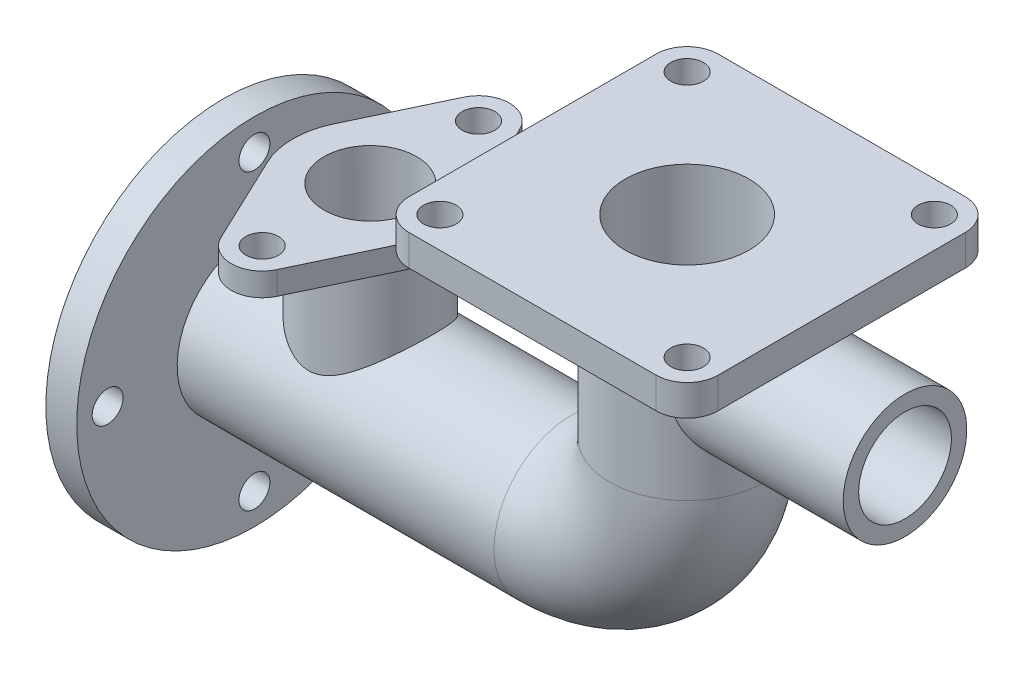
SolidWorks part; units mm, degrees
material "Titanium"
ref_plane "Front Plane" through (0, 0, 0) normal (0, 0, 1) x (1, 0, 0)
ref_plane "Top Plane" through (0, 0, 0) normal (0, 1, 0) x (1, 0, 0)
ref_plane "Right Plane" through (0, 0, 0) normal (1, 0, 0) x (0, 0, -1)
sketch "Sketch1" plane through (0, 0, 0) normal (0, 1, 0) x (1, 0, 0)
  circle A0 centre (0, 0) radius 10
  circle A1 centre (0, 0) radius 12.5
  dimension "D1" = 20
  dimension "D2" = 25
sketch "Sketch2" plane through (0, 0, 0) normal (0, 0, 1) x (1, 0, 0)
  line L0 (0, 0) -> (0, -31.25)
  line L1 (12.5, 0) -> (-12.5, 0) construction
  line L2 (-18.75, -50) -> (-75, -50)
  arc A0 (0, -31.25) -> (-18.75, -50) centre (-18.75, -31.25) cw
  dimension "D1" = 18.75
  dimension "D2" = 50
  dimension "D3" = 75
sweep "Sweep1" add profiles "Sketch1" path "Sketch2"
sketch "Sketch3" plane through (0, 0, 0) normal (0, 1, 0) x (1, 0, 0)
  line L1 (-20, 25) -> (20, 25)
  line L2 (-25, 20) -> (-25, -20)
  line L3 (-20, -25) -> (20, -25)
  line L4 (25, 20) -> (25, -20)
  line L5 (-25, 25) -> (25, -25) construction
  line L6 (-25, -25) -> (25, 25) construction
  arc A0 (20, -25) -> (25, -20) centre (20, -20) ccw
  arc A1 (20, 25) -> (25, 20) centre (20, 20) cw
  arc A2 (-25, -20) -> (-20, -25) centre (-20, -20) ccw
  arc A3 (-20, 25) -> (-25, 20) centre (-20, 20) ccw
  circle A4 centre (-20, 20) radius 2.64
  circle A5 centre (20, 20) radius 2.64
  circle A6 centre (-20, -20) radius 2.64
  circle A7 centre (20, -20) radius 2.64
  circle A8 centre (0, 0) radius 12.5 construction
  circle A9 centre (0, 0) radius 12.5
  point P0 (0, 0)
  dimension "D2" = 5
  dimension "D3" = 5.28
  dimension "D1" = 50
extrude "Boss-Extrude1" add sketch "Sketch3" against normal blind 5
sketch "Sketch4" plane through (0, 0, 0) normal (0, 0, 1) x (1, 0, 0)
  line L0 (0, -17.5) -> (35.25, -17.5) construction
  line L1 (0, -7.5) -> (35.25, -7.5)
  line L2 (0, -7.5) -> (0, -10)
  line L3 (0, -10) -> (35.25, -10)
  line L4 (35.25, -7.5) -> (35.25, -10)
  line L5 (25, 0) -> (20, 0) construction
  point P6 (0, -8.75)
  point P7 (0, 0)
  point P11 (0, 0)
  dimension "D1" = 15
  dimension "D2" = 20
  dimension "D3" = 17.5
  dimension "D4" = 35.25
revolve "Revolve1" add sketch "Sketch4" angle 360 about L0
sketch "Sketch5" plane through (0, 0, 0) normal (0, 0, 1) x (1, 0, 0)
  line L0 (0, -10) -> (35.25, -10) construction
  line L1 (0, -10) -> (35.25, -10)
  line L2 (0, -10) -> (0, -17.5)
  line L3 (0, -17.5) -> (35.25, -17.5)
  line L4 (35.25, -17.5) -> (35.25, -10)
revolve "Cut-Revolve1" cut sketch "Sketch5" angle 360 about L3
sketch "Sketch7" plane through (0, 0, 0) normal (0, 0, 1) x (1, 0, 0)
  line L0 (-75, -50) -> (-51.25, -50) construction
  line L1 (-61.25, -21.25) -> (-58.75, -21.25)
  line L2 (-61.25, -21.25) -> (-61.25, -50)
  line L3 (-61.25, -50) -> (-58.75, -50)
  line L4 (-58.75, -21.25) -> (-58.75, -50)
  line L5 (-75, -40) -> (-75, -60) construction
  line L6 (-18.75, -50) -> (-75, -50) construction
  line L7 (-51.25, -50) -> (-51.25, -21.25) construction
  point P10 (-53.1241, -21.25)
  point P12 (0, 0)
  point P13 (-51.25, -19.8357)
  dimension "D1" = 15
  dimension "D2" = 20
  dimension "D3" = 57.5
  dimension "D4" = 23.75
revolve "Revolve2" add sketch "Sketch7" angle 360 about L7
sketch "Sketch8" plane through (0, 0, 0) normal (0, 0, 1) x (1, 0, 0)
  line L0 (-58.75, -21.25) -> (-58.75, -50) construction
  line L1 (-58.75, -21.25) -> (-58.75, -50)
  line L2 (-58.75, -21.25) -> (-51.25, -21.25)
  line L3 (-51.25, -21.25) -> (-51.25, -50)
  line L4 (-51.25, -50) -> (-58.75, -50)
revolve "Cut-Revolve2" cut sketch "Sketch8" angle 360 about L3
sketch "Sketch9" plane through (0, -21.25, 0) normal (0, 1, 0) x (1, 0, 0)
  line L0 (-55.7675, 19.6429) -> (-62.5438, 5.3571)
  line L1 (-62.5438, -5.3571) -> (-55.7675, -19.6429)
  line L2 (-46.7325, -19.6429) -> (-39.9562, -5.3571)
  line L3 (-39.9562, 5.3571) -> (-46.7325, 19.6429)
  line L4 (-51.25, 17.5) -> (-51.25, -17.5) construction
  arc A0 (-62.5438, 5.3571) -> (-62.5438, -5.3571) centre (-51.25, 0) ccw
  arc A1 (-55.7675, -19.6429) -> (-46.7325, -19.6429) centre (-51.25, -17.5) ccw
  arc A2 (-39.9562, -5.3571) -> (-39.9562, 5.3571) centre (-51.25, 0) ccw
  arc A3 (-46.7325, 19.6429) -> (-55.7675, 19.6429) centre (-51.25, 17.5) ccw
  circle A4 centre (-51.25, 17.5) radius 2.64
  circle A5 centre (-51.25, -17.5) radius 2.64
  circle A6 centre (-51.25, 0) radius 10 construction
  circle A7 centre (-51.25, 0) radius 10
  point P2 (-51.25, 0)
  point P13 (-51.25, 0)
  dimension "D1" = 12.5
  dimension "D2" = 5
  dimension "D4" = 5.28
  dimension "D3" = 35
extrude "Boss-Extrude2" add sketch "Sketch9" against normal blind 3.75
sketch "Sketch10" plane through (-75, 0, 0) normal (-1, 0, 0) x (0, 0, 1)
  line L0 (-19.6429, -21.25) -> (-5.3571, -21.25) construction
  line L1 (-10, -50) -> (10, -50) construction
  circle A0 centre (0, -50) radius 28.75
  circle A1 centre (0, -50) radius 23.75 construction
  circle A2 centre (0, -26.25) radius 2.5
  circle A3 centre (23.75, -50) radius 2.5
  circle A4 centre (0, -73.75) radius 2.5
  circle A5 centre (-23.75, -50) radius 2.5
  circle A6 centre (0, -50) radius 10 construction
  circle A7 centre (0, -50) radius 12.5 construction
  circle A8 centre (0, -50) radius 12.5
  point P5 (0, -50)
  point P19 (0, -50)
  dimension "D1" = 47.5
  dimension "D2" = 5
  dimension "D3" = 4
extrude "Boss-Extrude3" add sketch "Sketch10" against normal blind 5
sketch "Sketch11" plane through (0, 0, 0) normal (0, 1, 0) x (1, 0, 0)
  circle A0 centre (0, 0) radius 10 construction
  circle A1 centre (0, 0) radius 10
sweep "Cut-Sweep1" cut profiles "Sketch11" path "Sketch2<2>"
sketch "Sketch2<2>" plane through (0, 0, 0) normal (0, 0, 1) x (1, 0, 0) same geometry as "Sketch2"
equation "\"D3@Sketch2\"=51.25+23.75"
